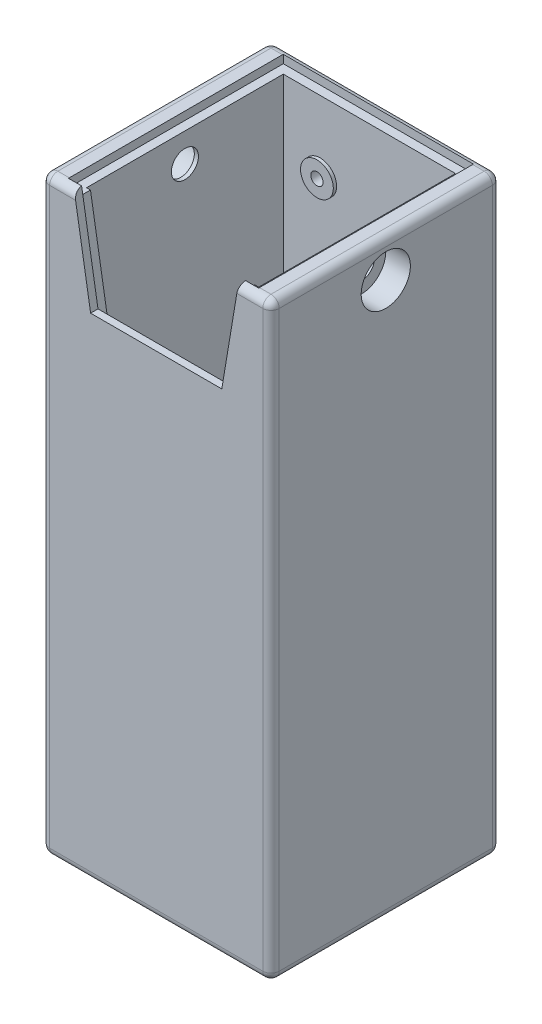
SolidWorks part; units mm, degrees
ref_plane "Ebene vorne" through (0, 0, 0) normal (0, 0, 1) x (1, 0, 0)
ref_plane "Ebene oben" through (0, 0, 0) normal (0, 1, 0) x (1, 0, 0)
ref_plane "Ebene rechts" through (0, 0, 0) normal (1, 0, 0) x (0, 0, -1)
sketch "Skizze1" plane through (0, 0, 0) normal (0, 1, 0) x (1, 0, 0)
  line L1 (14, 14) -> (-14, 14)
  line L2 (14, 14) -> (14, -14)
  line L3 (14, -14) -> (-14, -14)
  line L4 (-14, 14) -> (-14, -14)
  line L5 (14, 14) -> (-14, -14) construction
  line L6 (14, -14) -> (-14, 14) construction
  point P0 (0, 0)
  dimension "D1" = 28
  dimension "D2" = 28
extrude "Aufsatz-Linear austragen1" add sketch "Skizze1" along normal blind 72
sketch "Skizze2" plane through (0, 72, 0) normal (0, 1, 0) x (1, 0, 0)
  line L1 (-6.1, 5.1) -> (6.1, 5.1)
  line L2 (-6.1, 5.1) -> (-6.1, -5.1)
  line L3 (-6.1, -5.1) -> (6.1, -5.1)
  line L4 (6.1, 5.1) -> (6.1, -5.1)
  dimension "D1" = 10.2
  dimension "D2" = 12.2
  dimension "D3" = 5.1
  dimension "D4" = 6.1
extrude "Schnitt-Linear austragen1" cut sketch "Skizze2" against normal offset from surface (53 mm away) 19 up to face at (0, 0, 0)
sketch "Skizze3" plane through (0, 72, 0) normal (0, 1, 0) x (1, 0, 0)
  line L0 (14, 14) -> (-14, 14) construction
  line L1 (-10.5, 12) -> (10.5, 12)
  line L2 (-10.5, 12) -> (-10.5, -12)
  line L3 (-10.5, -12) -> (10.5, -12)
  line L4 (10.5, 12) -> (10.5, -12)
  line L5 (-14, 14) -> (-14, -14) construction
  line L6 (14, -14) -> (14, 14) construction
  line L7 (-14, -14) -> (14, -14) construction
  dimension "D1" = 2
  dimension "D2" = 3.5
  dimension "D3" = 3.5
  dimension "D4" = 2
extrude "Schnitt-Linear austragen2" cut sketch "Skizze3" against normal offset from surface (44 mm away) 9 up to face at (0, 19, 0)
sketch "Skizze4" plane through (0, 19, 0) normal (0, 1, 0) x (1, 0, 0)
  circle A0 centre (0, 0) radius 2.1
extrude "Schnitt-Linear austragen3" [suppressed] cut sketch "Skizze4" against normal blind 0.6
sketch "Skizze5" plane through (0, 0, 0) normal (0, 0, 1) x (1, 0, 0)
  line L0 (0, 0) -> (0, 28.6427) construction
  line L1 (-3, 0) -> (-3, 8)
  line L2 (14, 0) -> (-14, 0) construction
  line L3 (-3, 8) -> (-4.1, 8)
  line L4 (-4.1, 8) -> (-4.1, 19)
  line L5 (-4.1, 19) -> (0, 19)
  line L6 (0, 19) -> (0, 0)
  line L7 (0, 0) -> (-3, 0)
  dimension "D1" = 3
  dimension "D2" = 4.1
  dimension "D3" = 8
  dimension "D4" = 19
revolve "Schnitt-Rotation1" cut sketch "Skizze5" angle 360 about L0
sketch "Skizze6" plane through (0, 28, 0) normal (0, 1, 0) x (1, 0, 0)
  line L0 (6.1, -5.1) -> (6.1, 5.1) construction
  line L1 (6.1, 5.1) -> (-6.1, 5.1) construction
  line L2 (-6.1, 5.1) -> (-6.1, -5.1) construction
  line L3 (-6.1, -5.1) -> (6.1, -5.1) construction
  circle A1 centre (7.9, 4.6) radius 1.25
  circle A2 centre (-7.9, -4.6) radius 1.25
  dimension "D1" = 2.5
  dimension "D4" = 2.5
  dimension "D5" = 1.8
  dimension "D6" = 0.5
  dimension "D2" = 1.8
  dimension "D3" = 0.5
extrude "Schnitt-Linear austragen4" cut sketch "Skizze6" against normal blind 6
sketch "Skizze15" plane through (0, 0, 14) normal (0, 0, 1) x (1, 0, 0)
  line L0 (0, 0) -> (0, 92.0627) construction
  line L1 (-14, 0) -> (14, 0) construction
  line L2 (10, 72) -> (-10, 72)
  line L3 (-14, 72) -> (14, 72) construction
  line L4 (-10, 72) -> (-8, 60)
  line L5 (-8, 60) -> (8, 60)
  line L6 (10, 72) -> (8, 60)
  point P11 (0, 60)
  point P12 (0, 72)
  dimension "D1" = 10
  dimension "D2" = 8
  dimension "D3" = 12
extrude "Schnitt-Linear austragen13" cut sketch "Skizze15" against normal up to surface (2 mm away) up to face at (0, 50, 12)
sketch "Skizze7" plane through (0, 72, 0) normal (0, 1, 0) x (1, 0, 0)
  line L0 (10.5, 12) -> (-10.5, 12) construction
  line L1 (-11.6, 13.1) -> (11.6, 13.1)
  line L2 (-11.6, 13.1) -> (-11.6, -13.1)
  line L3 (-11.6, -13.1) -> (11.6, -13.1)
  line L4 (11.6, 13.1) -> (11.6, -13.1)
  line L5 (-10.5, 12) -> (-10.5, -12) construction
  line L6 (-10.5, -12) -> (-10, -12) construction
  line L7 (10.5, -12) -> (10.5, 12) construction
  dimension "D1" = 1.1
  dimension "D2" = 1.1
  dimension "D3" = 1.1
  dimension "D4" = 1.1
extrude "Schnitt-Linear austragen5" cut sketch "Skizze7" against normal blind 1
sketch "Skizze17" plane through (0, 0, 12) normal (0, 0, -1) x (-1, 0, 0)
  line L0 (-8, 60) -> (-8, 58.9) construction
  line L1 (-8, 58.9) -> (-10.0167, 71)
  line L3 (-10.0167, 71) -> (-9.8333, 71)
  line L4 (-9.8333, 71) -> (-8, 60)
  line L5 (-8, 60) -> (8, 60)
  line L6 (8, 60) -> (9.8333, 71)
  line L7 (-8, 58.9) -> (8, 58.9)
  line L8 (8, 58.9) -> (10.0167, 71)
  line L9 (9.8333, 71) -> (10.5, 71) construction
  line L10 (10.0167, 71) -> (9.8333, 71)
  line L11 (8, 60) -> (8, 58.9) construction
  dimension "D1" = 1.1
extrude "Schnitt-Linear austragen14" cut sketch "Skizze17" against normal blind 1.1
sketch "Skizze13" plane through (-14, 0, 0) normal (-1, 0, 0) x (0, 0, 1)
  line L0 (-14, 72) -> (14, 72) construction
  circle A0 centre (0, 67.5) radius 3
  dimension "D1" = 6
  dimension "D2" = 4.5
extrude "Schnitt-Linear austragen11" cut sketch "Skizze13" against normal blind 3
sketch "Skizze11" plane through (14, 0, 0) normal (1, 0, 0) x (0, 0, -1)
  line L0 (-14, 72) -> (14, 72) construction
  circle A0 centre (0, 67.5) radius 3
  dimension "D1" = 6
  dimension "D2" = 4.5
extrude "Schnitt-Linear austragen9" cut sketch "Skizze11" against normal blind 3
sketch "Skizze12" plane through (11, 0, 0) normal (1, 0, 0) x (0, 0, -1)
  circle A0 centre (0, 67.5) radius 1.625
  dimension "D1" = 3.25
extrude "Schnitt-Linear austragen10" cut sketch "Skizze12" against normal up to surface (0.5 mm away) up to face at (10.5, 49.5, 0)
sketch "Skizze14" plane through (-11, 0, 0) normal (-1, 0, 0) x (0, 0, 1)
  circle A0 centre (0, 67.5) radius 1.65
  dimension "D1" = 3.3
extrude "Schnitt-Linear austragen12" cut sketch "Skizze14" against normal up to surface (0.5 mm away) contours A0 up to face at (-10.5, 49.5, 0)
sketch "Skizze18" plane through (0, 0, -12) normal (0, 0, 1) x (1, 0, 0)
  line L0 (0, 0) -> (0, 107.3008) construction
  line L1 (11.6, 72) -> (-11.6, 72) construction
  circle A0 centre (-6, 62.4) radius 2
  circle A1 centre (6, 62.4) radius 2
  dimension "D1" = 4
  dimension "D2" = 6
  dimension "D3" = 9.6
extrude "Aufsatz-Linear austragen2" add sketch "Skizze18" along normal blind 0.4
sketch "Skizze19" plane through (0, 0, -11.6) normal (0, 0, 1) x (1, 0, 0)
  circle A0 centre (-6, 62.4) radius 0.75
  circle A1 centre (6, 62.4) radius 0.75
  dimension "D1" = 1.5
  dimension "D2" = 1.5
extrude "Schnitt-Linear austragen15" cut sketch "Skizze19" against normal offset from surface (1.6 mm away) 0.8 up to face at (0, 36, -14)
sketch "Skizze20" plane through (0, 0, 0) normal (0, 0, 1) x (1, 0, 0)
  line L0 (0, 0) -> (0, 16.3216) construction
  line L1 (-8, 0) -> (-8, 9.8867) construction
  line L2 (14, 0) -> (-14, 0) construction
  line L3 (-4.95, 0) -> (-4.95, 0.8)
  line L4 (-4.95, 0.8) -> (-5.45, 0.8)
  line L5 (-5.45, 0.8) -> (-5.45, 7)
  line L6 (-5.45, 7) -> (-4.95, 7)
  line L7 (-4.95, 7) -> (-4.95, 8.2)
  line L8 (-4.95, 8.2) -> (-8, 8.2)
  line L9 (-4.95, 0) -> (-8, 0)
  line L10 (-8, 8.2) -> (-8, 0)
  dimension "D1" = 2.55
  dimension "D2" = 3.05
  dimension "D3" = 3.05
  dimension "D4" = 0.8
  dimension "D5" = 6.2
  dimension "D6" = 1.2
  dimension "D7" = 8
revolve "Schnitt-Rotation2" cut sketch "Skizze20" angle 360 about L10
pattern_circular "Kreismuster1" count 4 every 90 about axis through (0, 0, 0) along (0, -1, 0) of "Schnitt-Rotation2"
fillet "Verrundung1" radius 1 13 edges at (-14, 0, 0) (0, 0, 14) (14, 0, 0) (14, 36, 14) (14, 36, -14) (-14, 36, -14) (0, 72, -14) (14, 72, 0) (12, 72, 14) (-12, 72, 14) (-14, 72, 0) (-14, 36, 14) (0, 0, -14)
